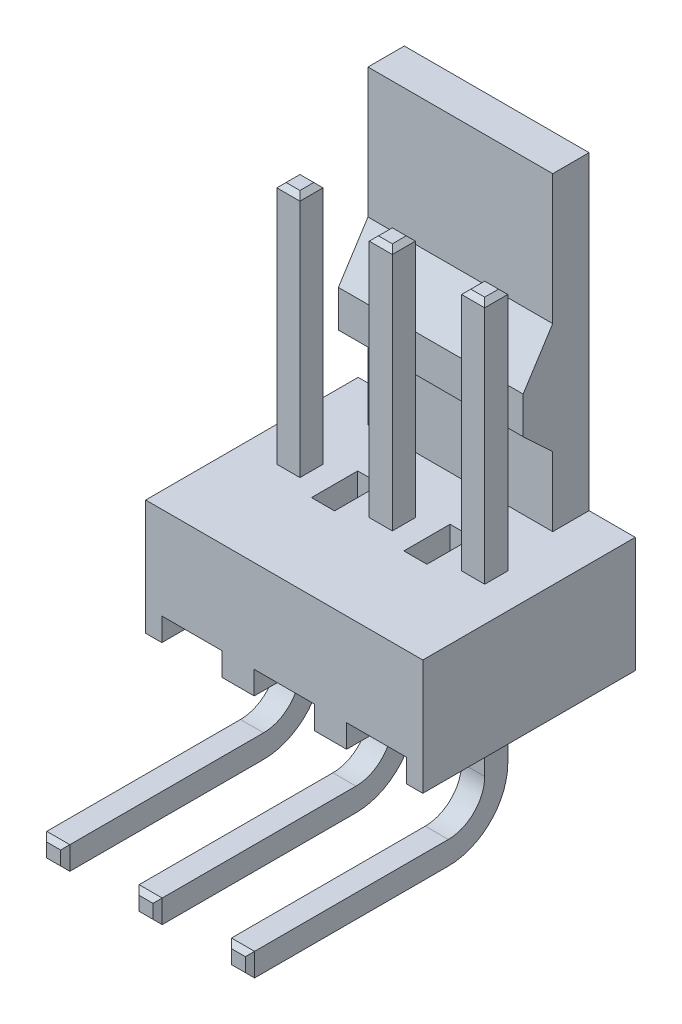
SolidWorks part; units mm, degrees
ref_plane "Front Plane" through (0, 0, 0) normal (0, 0, 1) x (1, 0, 0)
ref_plane "Top Plane" through (0, 0, 0) normal (0, 1, 0) x (1, 0, 0)
ref_plane "Right Plane" through (0, 0, 0) normal (1, 0, 0) x (0, 0, -1)
ref_plane "Plane1" through (0, -1.5875, 0) normal (0, -1, 0) x (1, 0, 0)
sketch "Sketch1" plane through (0, -1.5875, 0) normal (0, -1, 0) x (1, 0, 0)
  line L0 (-3.81, -2.8702) -> (2.54, -2.8702)
  line L1 (2.54, -2.8702) -> (2.54, 2.9718)
  line L2 (2.54, 2.9718) -> (-3.81, 2.9718)
  line L3 (-3.81, 2.9718) -> (-3.81, -2.8702)
extrude "Boss-Extrude1" add sketch "Sketch1" against normal blind 3.175
ref_plane "Plane2" through (2.54, 0, 0) normal (1, 0, 0) x (0, 0, -1)
sketch "Sketch2" plane through (2.54, 0, 0) normal (1, 0, 0) x (0, 0, -1)
  line L0 (0.651, 4.6355) -> (1.8702, 3.4925)
  line L1 (1.8702, 3.4925) -> (1.8702, 1.5875)
  line L2 (1.8702, 1.5875) -> (2.8702, 1.5875)
  line L3 (2.8702, 1.5875) -> (2.8702, 10.1125)
  line L4 (2.8702, 10.1125) -> (1.8702, 10.1125)
  line L5 (1.8702, 10.1125) -> (1.8702, 6.5405)
  line L6 (1.8702, 6.5405) -> (0.651, 4.6355)
extrude "Boss-Extrude2" add sketch "Sketch2" against normal blind 5.08
sketch "Sketch3" plane through (2.54, 0, 0) normal (1, 0, 0) x (0, 0, -1)
  line L0 (-2.9718, 1.5875) -> (2.8702, 1.5875)
  line L1 (2.8702, 1.5875) -> (2.8702, -1.5875)
  line L2 (2.8702, -1.5875) -> (-2.9718, -1.5875)
  line L3 (-2.9718, -1.5875) -> (-2.9718, 1.5875)
extrude "Boss-Extrude3" add sketch "Sketch3" along normal blind 1.27
sketch "Sketch4" plane through (0, 0, -2.8702) normal (0, 0, -1) x (-1, 0, 0)
  line L0 (-0.8255, -1.5875) -> (0.8255, -1.5875)
  line L1 (0.8255, -1.5875) -> (0.8255, -0.9525)
  line L2 (0.8255, -0.9525) -> (-0.8255, -0.9525)
  line L3 (-0.8255, -0.9525) -> (-0.8255, -1.5875)
extrude "Cut-Extrude1" cut sketch "Sketch4" against normal through all
sketch "Sketch5" plane through (0, -0.9525, 0) normal (0, -1, 0) x (1, 0, 0)
  line L0 (0.3175, -0.3175) -> (-0.3175, -0.3175)
  line L1 (-0.3175, -0.3175) -> (-0.3175, 0.3175)
  line L2 (-0.3175, 0.3175) -> (0.3175, 0.3175)
  line L3 (0.3175, 0.3175) -> (0.3175, -0.3175)
extrude "Boss-Extrude4" add sketch "Sketch5" along normal blind 3.6725
sketch "Sketch6" plane through (0, 0, 0.3175) normal (0, 0, 1) x (1, 0, 0)
  line L0 (0.3175, -3.99) -> (0.3175, -4.625)
  line L1 (0.3175, -4.625) -> (-0.3175, -4.625)
  line L2 (-0.3175, -4.625) -> (-0.3175, -3.99)
  line L3 (-0.3175, -3.99) -> (0.3175, -3.99)
extrude "Boss-Extrude5" add sketch "Sketch6" along normal blind 6.4543
sketch "Sketch7" plane through (0, 0, -2.8702) normal (0, 0, -1) x (-1, 0, 0)
  line L0 (1.7145, -1.5875) -> (3.3655, -1.5875)
  line L1 (3.3655, -1.5875) -> (3.3655, -0.9525)
  line L2 (3.3655, -0.9525) -> (1.7145, -0.9525)
  line L3 (1.7145, -0.9525) -> (1.7145, -1.5875)
extrude "Cut-Extrude2" cut sketch "Sketch7" against normal through all
sketch "Sketch8" plane through (0, -0.9525, 0) normal (0, -1, 0) x (1, 0, 0)
  line L0 (-2.2225, -0.3175) -> (-2.8575, -0.3175)
  line L1 (-2.8575, -0.3175) -> (-2.8575, 0.3175)
  line L2 (-2.8575, 0.3175) -> (-2.2225, 0.3175)
  line L3 (-2.2225, 0.3175) -> (-2.2225, -0.3175)
extrude "Boss-Extrude6" add sketch "Sketch8" along normal blind 3.6725
sketch "Sketch9" plane through (0, 0, 0.3175) normal (0, 0, 1) x (1, 0, 0)
  line L0 (-2.2225, -3.99) -> (-2.2225, -4.625)
  line L1 (-2.2225, -4.625) -> (-2.8575, -4.625)
  line L2 (-2.8575, -4.625) -> (-2.8575, -3.99)
  line L3 (-2.8575, -3.99) -> (-2.2225, -3.99)
extrude "Boss-Extrude7" add sketch "Sketch9" along normal blind 6.4543
sketch "Sketch10" plane through (0, 0, -2.8702) normal (0, 0, -1) x (-1, 0, 0)
  line L0 (-3.3655, -1.5875) -> (-1.7145, -1.5875)
  line L1 (-1.7145, -1.5875) -> (-1.7145, -0.9525)
  line L2 (-1.7145, -0.9525) -> (-3.3655, -0.9525)
  line L3 (-3.3655, -0.9525) -> (-3.3655, -1.5875)
extrude "Cut-Extrude3" cut sketch "Sketch10" against normal through all
sketch "Sketch11" plane through (0, -0.9525, 0) normal (0, -1, 0) x (1, 0, 0)
  line L0 (2.8575, -0.3175) -> (2.2225, -0.3175)
  line L1 (2.2225, -0.3175) -> (2.2225, 0.3175)
  line L2 (2.2225, 0.3175) -> (2.8575, 0.3175)
  line L3 (2.8575, 0.3175) -> (2.8575, -0.3175)
extrude "Boss-Extrude8" add sketch "Sketch11" along normal blind 3.6725
sketch "Sketch12" plane through (0, 0, 0.3175) normal (0, 0, 1) x (1, 0, 0)
  line L0 (2.8575, -4.625) -> (2.2225, -4.625)
  line L1 (2.2225, -4.625) -> (2.2225, -3.99)
  line L2 (2.2225, -3.99) -> (2.8575, -3.99)
  line L3 (2.8575, -3.99) -> (2.8575, -4.625)
extrude "Boss-Extrude9" add sketch "Sketch12" along normal blind 6.4543
sketch "Sketch13" plane through (0, 1.5875, 0) normal (0, 1, 0) x (-1, 0, 0)
  line L0 (-2.2225, -0.3175) -> (-2.8575, -0.3175)
  line L1 (-2.8575, -0.3175) -> (-2.8575, 0.3175)
  line L2 (-2.8575, 0.3175) -> (-2.2225, 0.3175)
  line L3 (-2.2225, 0.3175) -> (-2.2225, -0.3175)
extrude "Boss-Extrude10" add sketch "Sketch13" along normal blind 6.71
sketch "Sketch14" plane through (0, 1.5875, 0) normal (0, 1, 0) x (-1, 0, 0)
  line L0 (-0.3175, 0.3175) -> (0.3175, 0.3175)
  line L1 (0.3175, 0.3175) -> (0.3175, -0.3175)
  line L2 (0.3175, -0.3175) -> (-0.3175, -0.3175)
  line L3 (-0.3175, -0.3175) -> (-0.3175, 0.3175)
extrude "Boss-Extrude11" add sketch "Sketch14" along normal blind 6.71
sketch "Sketch15" plane through (0, 1.5875, 0) normal (0, 1, 0) x (-1, 0, 0)
  line L0 (2.8575, 0.3175) -> (2.8575, -0.3175)
  line L1 (2.8575, -0.3175) -> (2.2225, -0.3175)
  line L2 (2.2225, -0.3175) -> (2.2225, 0.3175)
  line L3 (2.2225, 0.3175) -> (2.8575, 0.3175)
extrude "Boss-Extrude12" add sketch "Sketch15" along normal blind 6.71
sketch "Sketch16" plane through (0, 1.5875, 0) normal (0, 1, 0) x (-1, 0, 0)
  line L0 (-1.5875, 0.635) -> (-1.5875, -0.635)
  line L1 (-1.5875, -0.635) -> (-0.9525, -0.635)
  line L2 (-0.9525, -0.635) -> (-0.9525, 0.635)
  line L3 (-0.9525, 0.635) -> (-1.5875, 0.635)
extrude "Cut-Extrude4" cut sketch "Sketch16" against normal blind 1.27
sketch "Sketch17" plane through (0, 1.5875, 0) normal (0, 1, 0) x (-1, 0, 0)
  line L0 (0.9525, 0.635) -> (0.9525, -0.635)
  line L1 (0.9525, -0.635) -> (1.5875, -0.635)
  line L2 (1.5875, -0.635) -> (1.5875, 0.635)
  line L3 (1.5875, 0.635) -> (0.9525, 0.635)
extrude "Cut-Extrude5" cut sketch "Sketch17" against normal blind 1.27
chamfer "Chamfer1" distance 0.127 angle 45 24 edges at (2.54, -3.99, 6.7718) (2.2225, -4.3075, 6.7718) (2.8575, -4.3075, 6.7718) (2.54, -4.625, 6.7718) (-0.3175, -4.3075, 6.7718) (0, -3.99, 6.7718) (0, -4.625, 6.7718) (0.3175, -4.3075, 6.7718) (-2.54, 8.2975, -0.3175) (-2.8575, 8.2975, 0) (-2.2225, 8.2975, 0) (-2.54, 8.2975, 0.3175) (-2.8575, -4.3075, 6.7718) (-2.54, -3.99, 6.7718) (-2.54, -4.625, 6.7718) (-2.2225, -4.3075, 6.7718) (-0.3175, 8.2975, 0) (0, 8.2975, -0.3175) (0, 8.2975, 0.3175) (0.3175, 8.2975, 0) (2.8575, 8.2975, 0) (2.54, 8.2975, 0.3175) (2.54, 8.2975, -0.3175) (2.2225, 8.2975, 0)
chamfer "Chamfer2" distance 0.7539 angle 32.619 1 edges at (0, 4.6355, -0.651) first distance on face at (0, 5.588, -1.2606)
fillet "Fillet1" radius 1 3 edges at (-2.54, -3.99, 0.3175) (0, -3.99, 0.3175) (2.54, -3.99, 0.3175) tangent propagation no
fillet "Fillet2" radius 1.635 3 edges at (2.54, -4.625, -0.3175) (-2.54, -4.625, -0.3175) (0, -4.625, -0.3175) tangent propagation no
ref_plane "Plane3" through (0, 0, 2.9718) normal (0, 0, 1) x (1, 0, 0)
sketch "Sketch18" plane through (0, 0, 2.9718) normal (0, 0, 1) x (1, 0, 0)
  line L0 (-2.2225, -4.625) -> (-2.8575, -4.625)
  line L1 (-2.2225, -4.625) -> (-2.8575, -4.625)
  line L2 (-2.8575, -4.625) -> (-2.8575, -3.99)
  line L3 (-2.8575, -4.625) -> (-2.8575, -3.99)
  line L4 (-2.8575, -3.99) -> (-2.2225, -3.99)
  line L5 (-2.8575, -3.99) -> (-2.2225, -3.99)
  line L6 (-2.2225, -3.99) -> (-2.2225, -4.625)
  line L7 (-2.2225, -3.99) -> (-2.2225, -4.625)
  line L8 (0.3175, -3.99) -> (0.3175, -4.625)
  line L9 (0.3175, -3.99) -> (0.3175, -4.625)
  line L10 (0.3175, -4.625) -> (-0.3175, -4.625)
  line L11 (0.3175, -4.625) -> (-0.3175, -4.625)
  line L12 (-0.3175, -3.99) -> (0.3175, -3.99)
  line L13 (-0.3175, -3.99) -> (0.3175, -3.99)
  line L14 (-0.3175, -4.625) -> (-0.3175, -3.99)
  line L15 (-0.3175, -4.625) -> (-0.3175, -3.99)
  line L16 (2.2225, -4.625) -> (2.2225, -3.99)
  line L17 (2.2225, -4.625) -> (2.2225, -3.99)
  line L18 (2.2225, -3.99) -> (2.8575, -3.99)
  line L19 (2.2225, -3.99) -> (2.8575, -3.99)
  line L20 (2.8575, -4.625) -> (2.2225, -4.625)
  line L21 (2.8575, -4.625) -> (2.2225, -4.625)
  line L22 (2.8575, -3.99) -> (2.8575, -4.625)
  line L23 (2.8575, -3.99) -> (2.8575, -4.625)
  line L24 (-2.8575, -3.99) -> (-2.2225, -4.625) construction
  line L25 (-2.2225, -3.99) -> (-2.8575, -4.625) construction
  line L26 (-0.3175, -4.625) -> (0.3175, -3.99) construction
  line L27 (0.3175, -4.625) -> (-0.3175, -3.99) construction
  line L28 (2.2225, -3.99) -> (2.8575, -4.625) construction
  line L29 (2.2225, -4.625) -> (2.8575, -3.99) construction
  circle A0 centre (-2.54, -4.3075) radius 0.449
  circle A1 centre (0, -4.3075) radius 0.449
  circle A2 centre (2.54, -4.3075) radius 0.449
